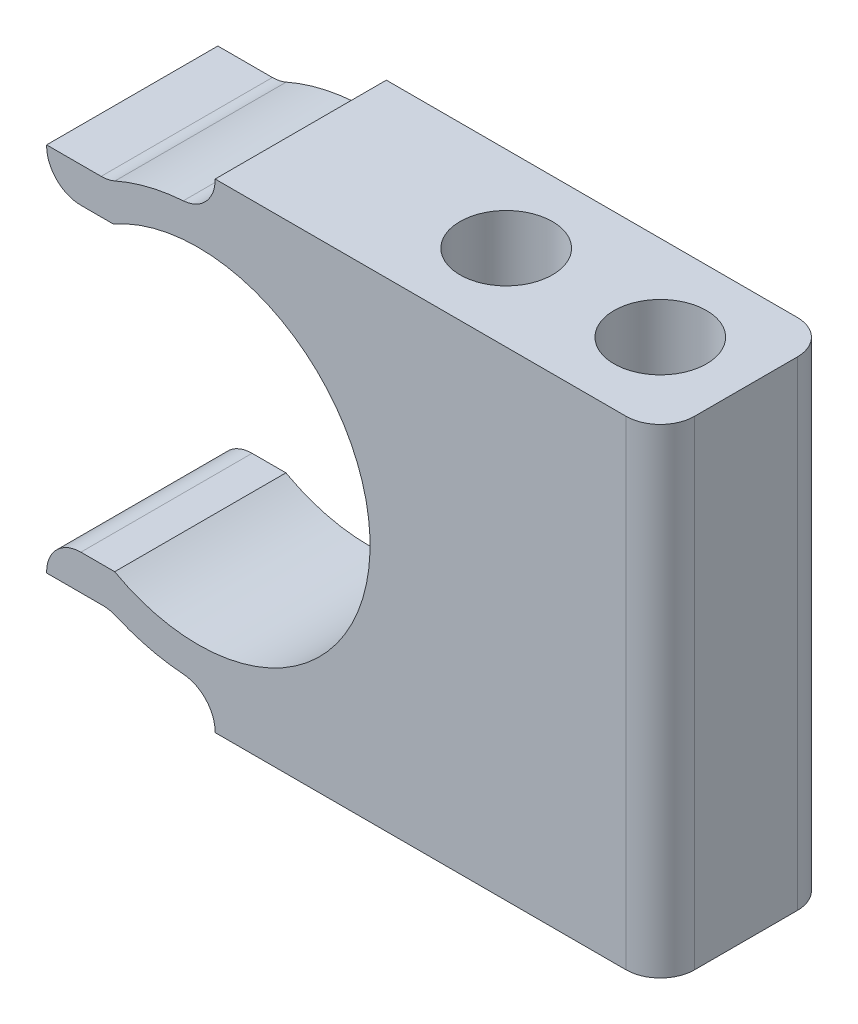
SolidWorks part; units mm, degrees
ref_plane "Front Plane" through (0, 0, 0) normal (0, 0, 1) x (1, 0, 0)
ref_plane "Top Plane" through (0, 0, 0) normal (0, 1, 0) x (1, 0, 0)
ref_plane "Right Plane" through (0, 0, 0) normal (1, 0, 0) x (0, 0, -1)
sketch "Sketch1" plane through (0, 0, 0) normal (0, 0, 1) x (1, 0, 0)
  line L0 (0, 0) -> (27, 0) construction
  line L2 (1, -11.9583) -> (1, -14)
  line L3 (5, 14) -> (27, 14)
  line L5 (9, -14) -> (27, -14)
  line L6 (27, 14) -> (27, -14)
  line L7 (5, 14) -> (1, 14)
  line L9 (9, -14) -> (1, -14)
  line L10 (1, 14) -> (1, 11.9583)
  line L11 (-8.8412, 0) -> (-10, 0) construction
  line L12 (-8.8412, 8.75) -> (-4.9437, 8.75)
  line L13 (-8.8412, 8.75) -> (-8.8412, -8.75) construction
  line L14 (-8.8412, -8.7938) -> (-4.8654, -8.7938)
  line L19 (-5.2173, 10.8065) -> (-8.8412, 10.8065)
  line L20 (-8.8412, 8.75) -> (-8.8412, 10.8065)
  line L23 (-5.1278, -10.8492) -> (-8.8412, -10.8492)
  line L24 (-8.8412, -8.7938) -> (-8.8412, -10.8492)
  arc A0 (-4.8654, -8.7938) -> (-4.9437, 8.75) centre (0, 0) ccw
  arc A1 (1, 11.9583) -> (-5.2173, 10.8065) centre (0, 0) ccw
  arc A2 (-5.1278, -10.8492) -> (1, -11.9583) centre (0, 0) ccw
  point P22 (-8.8412, 0)
  dimension "D1" = 20.1
  dimension "D2" = 24
  dimension "D3" = 27
  dimension "D4" = 28
  dimension "D5" = 18
  dimension "D6" = 8
  dimension "D7" = 17.5
extrude "Boss-Extrude1" add sketch "Sketch1" along normal blind 10
fillet "Fillet1" radius 2 8 edges at (1, -11.9583, 5) (1, 11.9583, 5) (-5.1278, -10.8492, 5) (-8.8412, 8.75, 5) (-8.8412, -8.7938, 5) (-5.2173, 10.8065, 5) (27, 0, 0) (27, 0, 10)
sketch "Sketch2" plane through (0, -14, 0) normal (0, -1, 0) x (1, 0, 0)
  line L0 (22, 5) -> (27, 5) construction
  line L1 (22, 5) -> (13, 5) construction
  line L2 (27, 8) -> (27, 2) construction
  line L3 (13, 5) -> (0, 5) construction
  line L6 (0, 5) -> (0, 0) construction
  circle A0 centre (13, 5) radius 2.7
  circle A1 centre (22, 5) radius 2.7
  point P7 (27, 5)
  dimension "D1" = 5.4
  dimension "D2" = 9
  dimension "D3" = 13
extrude "Cut-Extrude1" cut sketch "Sketch2" against normal through all
